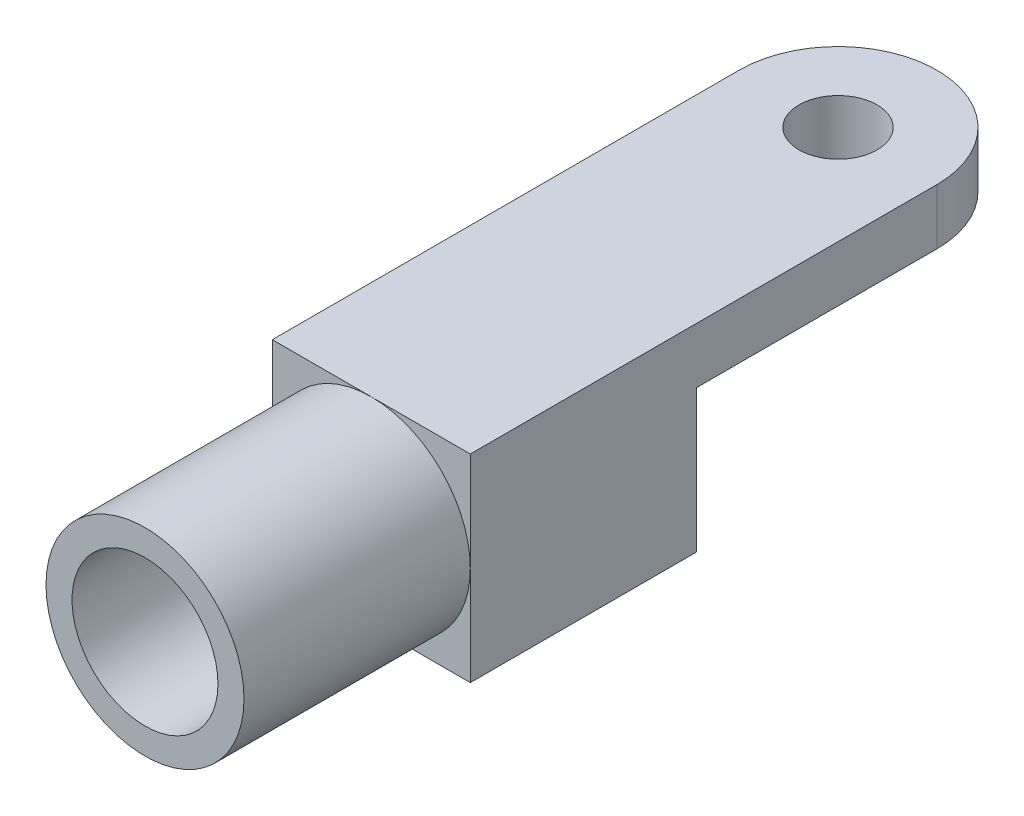
SolidWorks part; units mm, degrees
ref_plane "Front Plane" through (0, 0, 0) normal (0, 0, 1) x (1, 0, 0)
ref_plane "Top Plane" through (0, 0, 0) normal (0, 1, 0) x (1, 0, 0)
ref_plane "Right Plane" through (0, 0, 0) normal (1, 0, 0) x (0, 0, -1)
sketch "Sketch1" plane through (0, 0, 0) normal (0, 0, 1) x (1, 0, 0)
  circle A0 centre (0, 0) radius 3.275
  circle A1 centre (0, 0) radius 4.445
  dimension "D1" = 6.55
  dimension "D2" = 8.89
extrude "Boss-Extrude1" add sketch "Sketch1" along normal blind 10.16
sketch "Sketch2" plane through (0, 0, 0) normal (0, 0, -1) x (-1, 0, 0)
  line L1 (-4.445, 4.445) -> (4.445, 4.445)
  line L2 (-4.445, 4.445) -> (-4.445, -4.445)
  line L3 (-4.445, -4.445) -> (4.445, -4.445)
  line L4 (4.445, 4.445) -> (4.445, -4.445)
  circle A1 centre (0, 0) radius 4.445 construction
extrude "Boss-Extrude2" add sketch "Sketch2" along normal blind 25.4
sketch "Sketch3" plane through (0, -4.445, 0) normal (0, -1, 0) x (1, 0, 0)
  line L0 (4.445, -25.4) -> (-4.445, -25.4) construction
  line L1 (4.445, -25.4) -> (4.445, 0) construction
  line L2 (-4.445, -25.4) -> (-4.445, 0) construction
  line L3 (-4.445, -20.955) -> (-4.445, -25.4)
  line L4 (-4.445, -25.4) -> (4.445, -25.4)
  line L5 (4.445, -25.4) -> (4.445, -20.955)
  line L6 (4.445, -20.955) -> (-4.445, -20.955)
  circle A0 centre (0, -20.955) radius 4.445
  circle A1 centre (0, -20.955) radius 1.7526
  line M3 (-4.445, 0) -> (-4.445, -25.4)
  line M4 (-4.445, -25.4) -> (4.445, -25.4)
  line M5 (4.445, -25.4) -> (4.445, 0)
  dimension "D1" = 3.5052
extrude "Cut-Extrude1" cut sketch "Sketch3" against normal through all contours A0 L4 M5 | A0 M3 M4 | L6 A1 | L6 A1 | A1 region at (-3.4521, -4.445, -24.4071) region at (0, -4.445, -20.2112) region at (0, -4.445, -21.6988) region at (3.4521, -4.445, -24.4071)
sketch "Sketch4" plane through (-4.445, 0, 0) normal (-1, 0, 0) x (0, 0, 1)
  line L0 (-20.955, -4.445) -> (0, -4.445) construction
  line L1 (-10.16, -4.445) -> (-25.4, -4.445)
  line L2 (-10.16, -4.445) -> (-10.16, 1.9456)
  line L3 (-10.16, 1.9456) -> (-25.4, 1.9456)
  line L4 (-25.4, -4.445) -> (-25.4, 1.9456)
  line L5 (-25.4, 4.445) -> (-25.4, -4.445) construction
  line L9 (-17.78, -4.445) -> (-17.78, 1.9456) construction
  dimension "D1" = 15.24
  dimension "D2" = 6.3906
extrude "Cut-Extrude2" cut sketch "Sketch4" against normal through all
